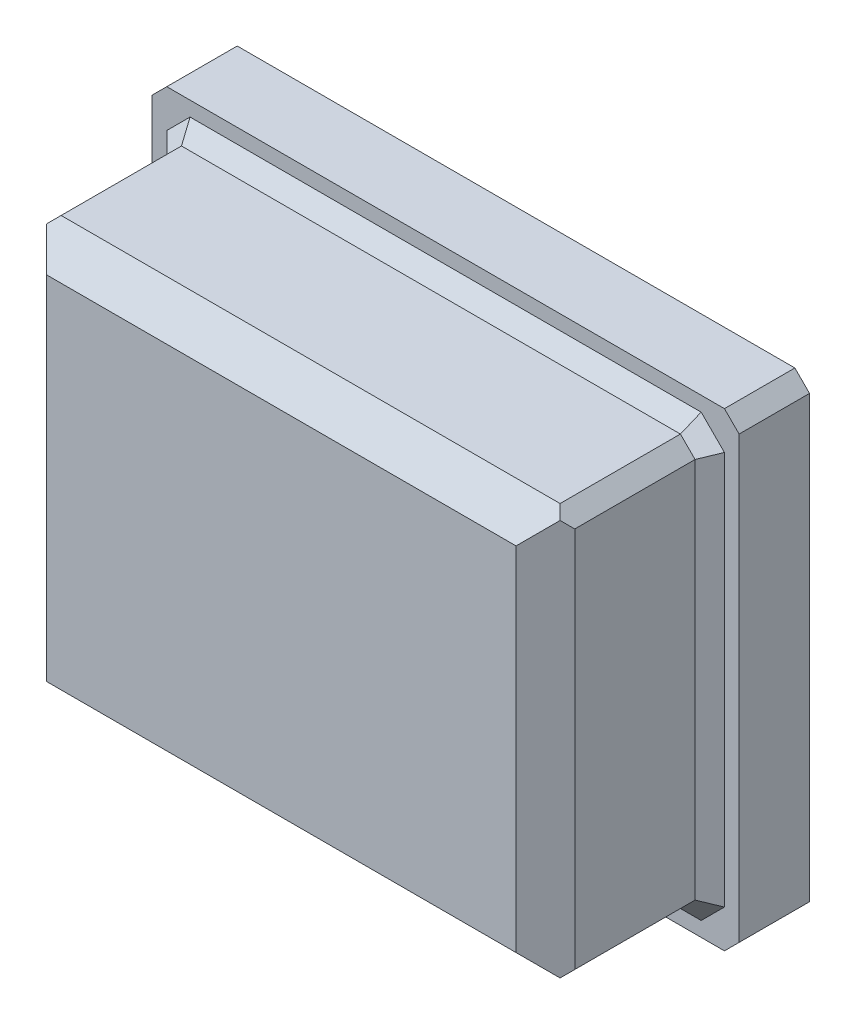
SolidWorks part; units mm, degrees
ref_plane "Front Plane" through (0, 0, 0) normal (0, 0, 1) x (1, 0, 0)
ref_plane "Top Plane" through (0, 0, 0) normal (0, 1, 0) x (1, 0, 0)
ref_plane "Right Plane" through (0, 0, 0) normal (1, 0, 0) x (0, 0, -1)
sketch "Sketch3" plane through (0, 0, 0) normal (0, 0, 1) x (1, 0, 0)
  line L0 (-1.3638, 0.8376) -> (-1.3138, 0.8876)
  line L1 (-1.3138, 0.8876) -> (0.5862, 0.8876)
  line L2 (-1.3638, 0.8376) -> (-1.3638, -0.6624)
  line L3 (-1.3138, -0.7124) -> (0.5862, -0.7124)
  line L4 (0.6362, 0.8376) -> (0.6362, -0.6624)
  line L5 (0.5862, 0.8876) -> (0.6362, 0.8376)
  line L6 (0.5862, -0.7124) -> (0.6362, -0.6624)
  line L7 (-1.3638, -0.6624) -> (-1.3138, -0.7124)
  point P0 (-1.3638, 0.8876)
  point P1 (0.6362, -0.7124)
  point P2 (-1.3638, -0.7124)
  point P3 (0.6362, 0.8876)
  dimension "D1" = 1.6
  dimension "D2" = 2
extrude "Boss-Extrude1" add sketch "Sketch3" along normal blind 0.24
sketch "Sketch4" plane through (0, 0, 0.24) normal (0, 0, 1) x (1, 0, 0)
  line L0 (-1.2638, 0.7376) -> (-1.2138, 0.7876)
  line L1 (-1.2138, 0.7876) -> (0.4862, 0.7876)
  line L2 (-1.2638, 0.7376) -> (-1.2638, -0.5624)
  line L3 (-1.2138, -0.6124) -> (0.4862, -0.6124)
  line L4 (0.5362, 0.7376) -> (0.5362, -0.5624)
  line L5 (0.4862, 0.7876) -> (0.5362, 0.7376)
  line L6 (0.4862, -0.6124) -> (0.5362, -0.5624)
  line L7 (-1.2638, -0.5624) -> (-1.2138, -0.6124)
  point P0 (-1.2638, 0.7876)
  point P1 (0.5362, -0.6124)
  point P2 (-1.2638, -0.6124)
  point P3 (0.5362, 0.7876)
  dimension "D1" = 0.1
  dimension "D2" = 0.1
  dimension "D3" = 0.1
  dimension "D4" = 0.1
extrude "Boss-Extrude2" add sketch "Sketch4" along normal blind 0.56
chamfer "Chamfer1" distance 0.1 angle 45 4 edges at (-0.3638, 0.7876, 0.8) (0.5362, 0.0876, 0.8) (-0.3638, -0.6124, 0.8) (-1.2638, 0.0876, 0.8)
chamfer "Chamfer2" distance 0.05 angle 45 8 edges at (-1.2388, 0.7626, 0.24) (-0.3638, 0.7876, 0.24) (0.5112, 0.7626, 0.24) (0.5362, 0.0876, 0.24) (0.5112, -0.5874, 0.24) (-0.3638, -0.6124, 0.24) (-1.2388, -0.5874, 0.24) (-1.2638, 0.0876, 0.24)
